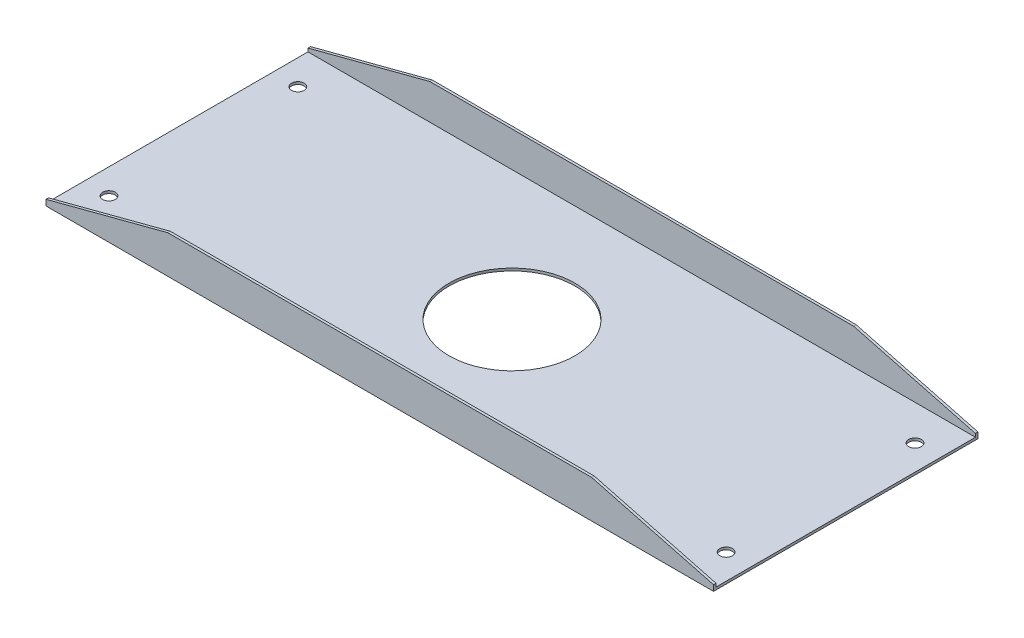
SolidWorks part; units mm, degrees
ref_plane "Спереди" through (0, 0, 0) normal (0, 0, 1) x (1, 0, 0)
ref_plane "Сверху" through (0, 0, 0) normal (0, 1, 0) x (1, 0, 0)
ref_plane "Справа" through (0, 0, 0) normal (1, 0, 0) x (0, 0, -1)
sketch "Эскиз1" plane through (0, 0, 0) normal (1, 0, 0) x (0, 0, -1)
  line L0 (-105, 0) -> (105, 0)
  line L1 (105, 0) -> (105, 30)
  line L2 (-105, 0) -> (-105, 30)
  dimension "D1" = 210
  dimension "D2" = 30
  dimension "D3" = 30
extrude "Вытянуть-Тонкостенный1" add sketch "Эскиз1" along normal blind 530 thin thin type one direction wall 2
sketch "Эскиз2" plane through (0, 0, -105) normal (0, 0, -1) x (-1, 0, 0)
  line L0 (-530, 0) -> (-530, 4.6148)
  line L1 (-530, 30) -> (-530, 0) construction
  line L2 (-530, 4.6148) -> (-433.2757, 30)
  line L3 (-530, 30) -> (0, 30) construction
  line L4 (-433.2757, 30) -> (-96.7243, 30)
  line L5 (-96.7243, 30) -> (0, 4.6148)
  line L6 (0, 30) -> (0, 0) construction
  line L7 (0, 4.6148) -> (0, 0)
  line L8 (0, 0) -> (-530, 0)
extrude "Вырез-Вытянуть2" cut sketch "Эскиз2" against normal through all flip side to cut
sketch "Эскиз3" plane through (0, 2, 0) normal (0, 1, 0) x (1, 0, 0)
  line L0 (20, 115.302) -> (20, -116.3672) construction
  line L1 (0, 103) -> (0, -103) construction
  line L2 (0, 105) -> (96.7243, 105) construction
  line L3 (510, 126.018) -> (510, -161.4271) construction
  line L4 (530, 103) -> (530, -103) construction
  line L5 (0, 103) -> (530, -103) construction
  line L6 (530, 103) -> (0, -103) construction
  circle A0 centre (20, 75) radius 5
  circle A1 centre (20, -75) radius 5
  circle A2 centre (510, 75) radius 5
  circle A3 centre (510, -75) radius 5
  circle A4 centre (265, 0) radius 50
  dimension "D2" = 30
  dimension "D1" = 20
  dimension "D3" = 150
  dimension "D4" = 20
extrude "Вырез-Вытянуть3" cut sketch "Эскиз3" against normal through all
